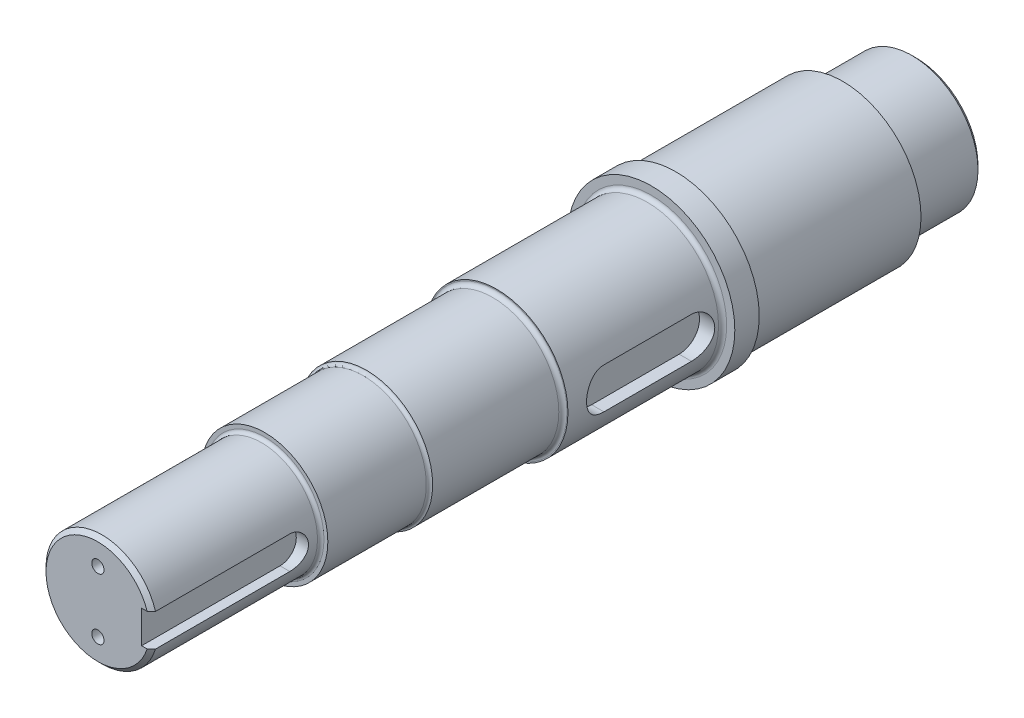
SolidWorks part; units mm, degrees
ref_plane "前视基准面" through (0, 0, 0) normal (0, 0, 1) x (1, 0, 0)
ref_plane "上视基准面" through (0, 0, 0) normal (0, 1, 0) x (1, 0, 0)
ref_plane "右视基准面" through (0, 0, 0) normal (1, 0, 0) x (0, 0, -1)
sketch "草图1" plane through (0, 0, 0) normal (0, 0, 1) x (1, 0, 0)
  circle A0 centre (0, 0) radius 32.5
  dimension "D1" = 65
extrude "凸台-拉伸1" add sketch "草图1" along normal blind 36
sketch "草图2" plane through (0, 0, 36) normal (0, 0, 1) x (1, 0, 0)
  circle A0 centre (0, 0) radius 38.5
  dimension "D1" = 77
extrude "凸台-拉伸2" add sketch "草图2" along normal blind 82
sketch "草图3" plane through (0, 0, 118) normal (0, 0, 1) x (1, 0, 0)
  circle A0 centre (0, 0) radius 41
  dimension "D1" = 82
extrude "凸台-拉伸3" add sketch "草图3" along normal blind 12
sketch "草图4" plane through (0, 0, 130) normal (0, 0, 1) x (1, 0, 0)
  circle A0 centre (0, 0) radius 35
  dimension "D1" = 70
extrude "凸台-拉伸4" add sketch "草图4" along normal blind 76
sketch "草图5" plane through (0, 0, 206) normal (0, 0, 1) x (1, 0, 0)
  circle A0 centre (0, 0) radius 32.5
  dimension "D1" = 65
extrude "凸台-拉伸5" add sketch "草图5" along normal blind 64
sketch "草图6" plane through (0, 0, 270) normal (0, 0, 1) x (1, 0, 0)
  circle A0 centre (0, 0) radius 31
  dimension "D1" = 62
extrude "凸台-拉伸6" add sketch "草图6" along normal blind 50
sketch "草图7" plane through (0, 0, 320) normal (0, 0, 1) x (1, 0, 0)
  circle A0 centre (0, 0) radius 27.5
  dimension "D1" = 55
extrude "凸台-拉伸7" add sketch "草图7" along normal blind 82
fillet "圆角1" radius 2 2 edges at (32.5, 0, 206) (35, 0, 130)
fillet "圆角2" radius 1.6 2 edges at (27.5, 0, 320) (31, 0, 270)
chamfer "倒角1" distance 2 angle 45 2 edges at (32.5, 0, 0) (27.5, 0, 402)
ref_plane "基准面1" through (27.5, 0, 0) normal (1, 0, 0) x (0, 0, -1)
sketch "草图8" plane through (27.5, 0, 0) normal (1, 0, 0) x (0, 0, -1)
  line L0 (-202.5, 0) -> (-135.849, 0) construction
  line L1 (-130, 37) -> (-130, -37) construction
  line L2 (-186.8597, 10) -> (-143.8597, 10)
  line L4 (-186.8597, -10) -> (-143.8597, -10)
  arc A0 (-143.8597, -10) -> (-143.8597, 10) centre (-143.8597, 0) ccw
  arc A1 (-186.8597, 10) -> (-186.8597, -10) centre (-186.8597, 0) ccw
  dimension "D4" = 20
  dimension "D5" = 20
  dimension "D1" = 20
  dimension "D2" = 10
  dimension "D3" = 43
  dimension "D6" = 13.8597
extrude "切除-拉伸1" cut sketch "草图8" along normal blind 29
ref_plane "基准面2" through (21.5, 0, 0) normal (1, 0, 0) x (0, 0, -1)
sketch "草图9" plane through (21.5, 0, 0) normal (1, 0, 0) x (0, 0, -1)
  line L0 (-409.335, 0) -> (-328.903, 0) construction
  line L1 (-402, 25.5) -> (-402, -25.5) construction
  line L2 (-402, 8) -> (-334, 8)
  line L3 (-402, 8) -> (-402, -8)
  line L4 (-402, -8) -> (-334, -8)
  arc A0 (-334, -8) -> (-334, 8) centre (-334, 0) ccw
  dimension "D1" = 8
  dimension "D2" = 16
  dimension "D3" = 68
extrude "切除-拉伸2" cut sketch "草图9" along normal blind 20
sketch "草图10" plane through (0, 0, 402) normal (0, 0, 1) x (1, 0, 0)
  line L0 (0, 18.073) -> (0, -20.554) construction
  line L1 (-19.49, 0) -> (17.896, 0) construction
  circle A0 centre (0, 15) radius 3
  circle A1 centre (0, -15) radius 3
  dimension "D1" = 6
  dimension "D2" = 15
extrude "切除-拉伸3" cut sketch "草图10" against normal blind 20
